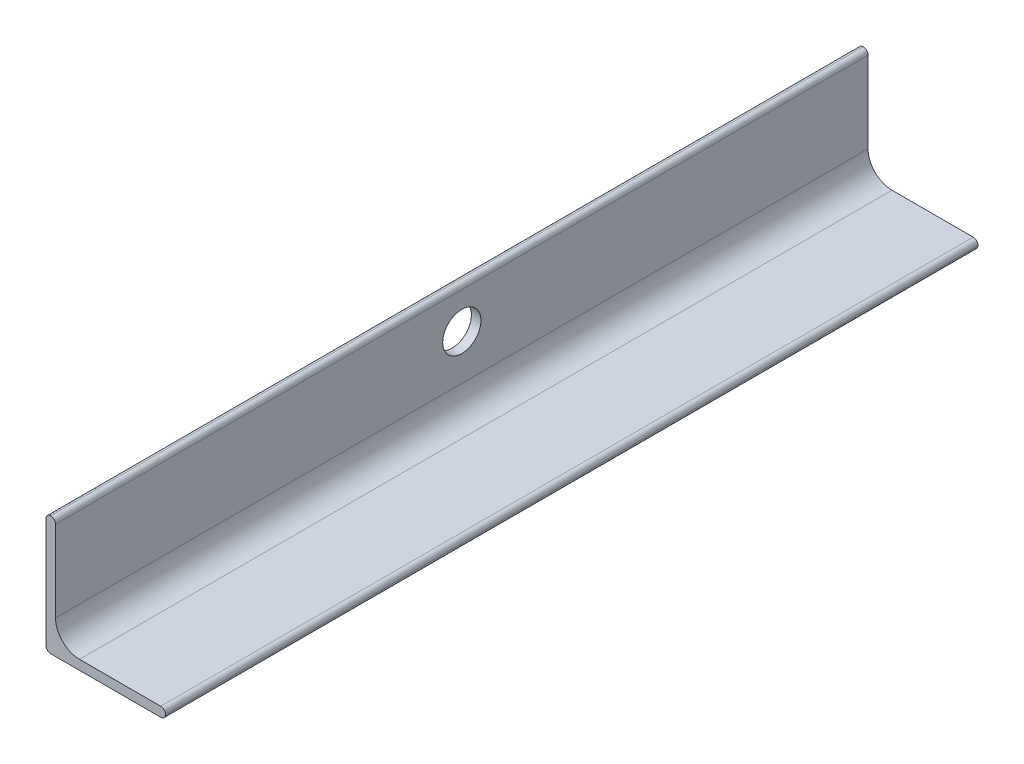
SolidWorks part; units mm, degrees
material "Q235锻制"
ref_plane "前视基准面" through (0, 0, 0) normal (0, 0, 1) x (1, 0, 0)
ref_plane "上视基准面" through (0, 0, 0) normal (0, 1, 0) x (1, 0, 0)
ref_plane "右视基准面" through (0, 0, 0) normal (1, 0, 0) x (0, 0, -1)
sketch "草图1" plane through (0, 0, 0) normal (0, 0, 1) x (1, 0, 0)
  line L0 (0, 0) -> (25, 0)
  line L1 (55, 0) -> (-55, 0) construction
  line L2 (25, 0) -> (25, 2)
  line L3 (25, 2) -> (7, 2)
  line L4 (2, 7) -> (2, 25)
  line L5 (2, 25) -> (0, 25)
  line L6 (0, -55) -> (0, 55) construction
  line L7 (0, 25) -> (0, 0)
  arc A0 (7, 2) -> (2, 7) centre (7, 7) cw
  dimension "D5" = 5
  dimension "D1" = 25
  dimension "D2" = 25
  dimension "D3" = 2
  dimension "D4" = 2
extrude "凸台-拉伸1" add sketch "草图1" along normal blind 170
fillet "圆角1" radius 1 5 edges at (0, 25, 85) (25, 2, 85) (25, 0, 85) (0, 0, 85) (2, 25, 85)
sketch "草图2" plane through (2, 0, 0) normal (1, 0, 0) x (0, 0, -1)
  line L0 (0, 7) -> (0, 24) construction
  circle A0 centre (-85, 16.4019) radius 4
  dimension "D1" = 8
  dimension "D2" = 85
extrude "切除-拉伸1" cut sketch "草图2" against normal through all
